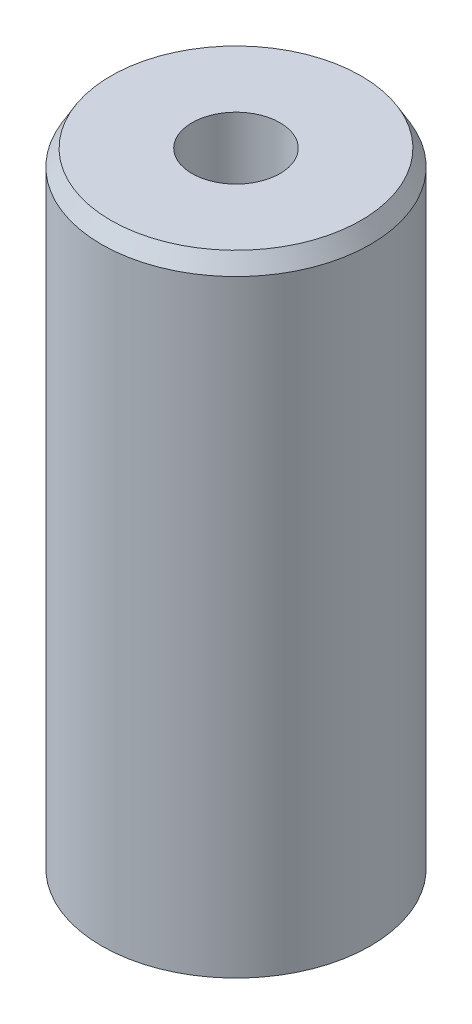
SolidWorks part; units mm, degrees
ref_plane "Front Plane" through (0, 0, 0) normal (0, 0, 1) x (1, 0, 0)
ref_plane "Top Plane" through (0, 0, 0) normal (0, 1, 0) x (1, 0, 0)
ref_plane "Right Plane" through (0, 0, 0) normal (1, 0, 0) x (0, 0, -1)
sketch "Sketch1" plane through (0, 0, 0) normal (0, 1, 0) x (1, 0, 0)
  circle A0 centre (0, 0) radius 7.5
  dimension "SHAFT_OD" = 15
extrude "Boss-Extrude1" add sketch "Sketch1" along normal blind 35.3084
sketch "Sketch2" plane through (0, 0, 0) normal (0, 1, 0) x (1, 0, 0)
  circle A0 centre (0, 0) radius 2.4576
  dimension "BORE_D" = 4.9152
extrude "Cut-Extrude1" cut sketch "Sketch2" along normal through all
chamfer "Chamfer1" distance 0.9023 angle 30 2 edges at (0, 35.3084, 7.5) (0, 0, 7.5) first distance on face at (0, 35.3084, 7.5) first distance on face at (0, 0, 2.4576)
